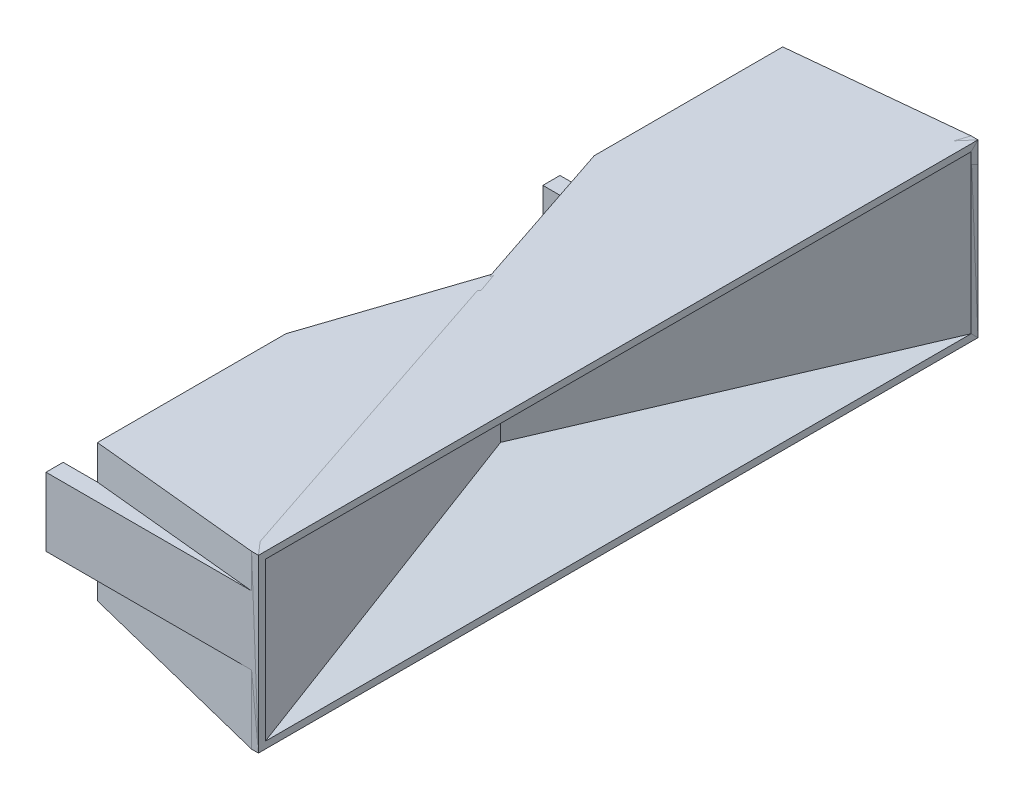
SolidWorks part; units mm, degrees
ref_plane "Front Plane" through (0, 0, 0) normal (0, 0, 1) x (1, 0, 0)
ref_plane "Top Plane" through (0, 0, 0) normal (0, 1, 0) x (1, 0, 0)
ref_plane "Right Plane" through (0, 0, 0) normal (1, 0, 0) x (0, 0, -1)
sketch "Sketch1" plane through (0, 0, 0) normal (1, 0, 0) x (0, 0, -1)
  line L0 (-103, 23) -> (103, 23)
  line L1 (-105, -25) -> (105, -25)
  line L2 (-105, -25) -> (-105, 25)
  line L3 (-105, 25) -> (105, 25)
  line L4 (105, -25) -> (105, 25)
  line L5 (-105, -25) -> (105, 25) construction
  line L6 (-105, 25) -> (105, -25) construction
  line L7 (103, -23) -> (103, 23)
  line L8 (-103, -23) -> (103, -23)
  line L9 (-103, -23) -> (-103, 23)
  point P0 (0, 0)
  dimension "D1" = 50
  dimension "D2" = 210
  dimension "D3" = 2
extrude "Boss-Extrude3" add sketch "Sketch1" along normal blind 52
sketch "Sketch3" plane through (0, 0, 0) normal (-1, 0, 0) x (0, 0, 1)
  line L4 (-105, 25) -> (-105, -25)
  line L5 (-105, -25) -> (105, -25)
  line L6 (105, -25) -> (105, 25)
  line L7 (105, 25) -> (-105, 25)
  line L8 (-105, 25) -> (-105, -25)
  line L9 (-105, -25) -> (105, -25)
  line L10 (105, -25) -> (105, 25)
  line L11 (105, 25) -> (-105, 25)
  dimension "D1" = 0
extrude "Boss-Extrude4" add sketch "Sketch3" against normal blind 2
chamfer "Chamfer1" distance 5 distance2 50 1 edges at (2, 0, 103) first distance on face at (2, 0, 0)
chamfer "Chamfer2" distance 10 distance2 50 1 edges at (2, -23, -2.5) first distance on face at (2, 0, -2.5)
chamfer "Chamfer3" distance 150 distance2 50 1 edges at (2, 5, -103) first distance on face at (2, 5, -2.5)
chamfer "Chamfer4" distance 150 distance2 50 1 edges at (0, 0, -105) first distance on face at (0, 0, 0)
chamfer "Chamfer5" distance 10 distance2 50 1 edges at (0, -25, 75) first distance on face at (0, 0, 75)
chamfer "Chamfer6" distance 5 distance2 50 1 edges at (0, 5, 105) first distance on face at (0, 5, 75)
sketch "Sketch4" plane through (0, 0, 0) normal (-1, 0, 0) x (0, 0, 1)
  line L0 (98, 23) -> (47, 23)
  line L1 (47, 23) -> (47, -13)
  line L2 (47, -13) -> (98, -13)
  line L3 (98, -13) -> (98, 23)
  line L4 (45, -15) -> (100, -15)
  line L5 (100, -15) -> (100, 25)
  line L6 (100, 25) -> (45, 25)
  line L7 (45, 25) -> (45, -15)
  line L8 (45, -15) -> (100, -15)
  line L9 (100, -15) -> (100, 25)
  line L10 (100, 25) -> (45, 25)
  line L11 (45, 25) -> (45, -15)
  dimension "D1" = 0
  dimension "D2" = 2
extrude "Cut-Extrude2" cut sketch "Sketch4" against normal blind 2 contours L0 L1 L2 L3
sketch "Sketch5" plane through (0, 0, 0) normal (-1, 0, 0) x (0, 0, 1)
  line L0 (100, -15) -> (100, 25) construction
  line L1 (100, -5) -> (105, -5)
  line L2 (100, -5) -> (100, 15)
  line L3 (100, 15) -> (105, 15)
  line L4 (105, -5) -> (105, 15)
  line L5 (45, 25) -> (45, -15) construction
  line L6 (45, -5) -> (40, -5)
  line L7 (45, -5) -> (45, 15)
  line L8 (45, 15) -> (40, 15)
  line L9 (40, -5) -> (40, 15)
  line L10 (98, -13) -> (98, 23) construction
  point P14 (98, 5)
  point P15 (100, 5)
  dimension "D1" = 5
  dimension "D2" = 5
  dimension "D3" = 20
extrude "Boss-Extrude5" add sketch "Sketch5" along normal blind 10 separate body
sketch "Sketch6" plane through (0, 0, 0) normal (1, 0, 0) x (0, 0, -1)
  line L4 (-45, 15) -> (-45, -5)
  line L5 (-45, -5) -> (-40, -5)
  line L6 (-40, -5) -> (-40, 15)
  line L7 (-40, 15) -> (-45, 15)
  line L8 (-45, 15) -> (-45, -5)
  line L9 (-45, -5) -> (-40, -5)
  line L10 (-40, -5) -> (-40, 15)
  line L11 (-40, 15) -> (-45, 15)
  line L12 (-100, -5) -> (-100, 15)
  line L13 (-100, 15) -> (-105, 15)
  line L14 (-105, 15) -> (-105, -5)
  line L15 (-105, -5) -> (-100, -5)
  line L16 (-100, -5) -> (-100, 15)
  line L17 (-100, 15) -> (-105, 15)
  line L18 (-105, 15) -> (-105, -5)
  line L19 (-105, -5) -> (-100, -5)
  dimension "D1" = 0
  dimension "D2" = 0
extrude "Boss-Extrude6" add sketch "Sketch6" along normal blind 52
sketch "Sketch7" plane through (0, -13, 0) normal (0, 1, 0) x (1, 0, 0)
  line L4 (52, -103) -> (52, 103)
  line L5 (52, 103) -> (2, -47)
  line L6 (2, -47) -> (2, -98)
  line L7 (2, -98) -> (52, -103)
  line L8 (52, -103) -> (52, 103)
  line L9 (52, 103) -> (2, -47)
  line L10 (2, -47) -> (2, -98)
  line L11 (2, -98) -> (52, -103)
  dimension "D1" = 0
extrude "Cut-Extrude3" cut sketch "Sketch7" along normal up to surface (36 mm away) up to face at (18, 23, 48.3333)
mirror "Mirror1" about plane through (0, 0, 0) normal (0, 0, 1) of bodies 111
hole_wizard "CBORE for M5 Hex Head Bolt2" positions "Sketch11" profile "Sketch12" counterbore size "M5" standard "ANSI Metric" end condition through all
sketch "Sketch11" plane through (0, 0, -40) normal (0, 0, 1) x (1, 0, 0)
  line L8 (0, -5) -> (0, 15)
  line L9 (0, 15) -> (-10, 15)
  line L10 (-10, 15) -> (-10, -5)
  line L11 (-10, -5) -> (0, -5)
  line L12 (0, -5) -> (0, 15)
  line L13 (0, 15) -> (-10, 15)
  line L14 (-10, 15) -> (-10, -5)
  line L15 (-10, -5) -> (0, -5)
  line L16 (-10, -5) -> (0, 15)
  point P18 (-5, 5)
  dimension "D1" = 0
sketch "Sketch12" plane through (-5, 5, -40) normal (1, 0, 0) x (0, -1, 0)
  line L0 (0, 0) -> (0, 65)
  line L1 (0, 65) -> (2.25, 65)
  line L3 (2.25, 65) -> (2.25, 4.2)
  line L4 (2.25, 4.2) -> (2.5, 4.2)
  line L5 (2.5, 4.2) -> (2.5, 0)
  line L7 (2.5, 0) -> (0, 0)
  line L11 (0, -6.35) -> (0, 107.95) construction
  dimension "Thru Hole Dia." = 4.5
  dimension "Thru Hole Depth" = 65
  dimension "C'Bore Dia." = 5
  dimension "C'Bore Depth" = 4.2
hole_wizard "CBORE for M5 Hex Head Bolt3" positions "Sketch13" profile "Sketch14" counterbore size "M5" standard "ANSI Metric" end condition through all
sketch "Sketch13" plane through (0, 0, -105) normal (0, 0, -1) x (-1, 0, 0)
  point P0 (5, 5)
sketch "Sketch14" plane through (-5, 5, -105) normal (1, 0, 0) x (0, 1, 0)
  line L0 (0, 0) -> (0, 210)
  line L1 (0, 210) -> (2.25, 210)
  line L3 (2.25, 210) -> (2.25, 4.2)
  line L4 (2.25, 4.2) -> (2.5, 4.2)
  line L5 (2.5, 4.2) -> (2.5, 0)
  line L7 (2.5, 0) -> (0, 0)
  line L11 (0, -6.35) -> (0, 107.95) construction
  dimension "Thru Hole Dia." = 4.5
  dimension "Thru Hole Depth" = 210
  dimension "C'Bore Dia." = 5
  dimension "C'Bore Depth" = 4.2
